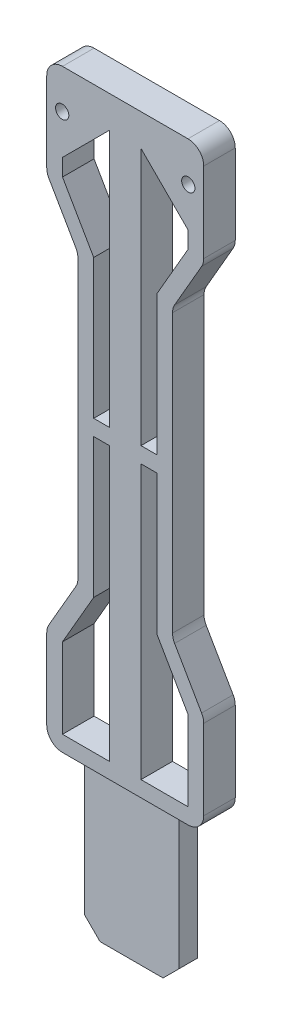
SolidWorks part; units mm, degrees
ref_plane "前视基准面" through (0, 0, 0) normal (0, 0, 1) x (1, 0, 0)
ref_plane "上视基准面" through (0, 0, 0) normal (0, 1, 0) x (1, 0, 0)
ref_plane "右视基准面" through (0, 0, 0) normal (1, 0, 0) x (0, 0, -1)
other "Configuration Table"
sketch "草图1" plane through (0, 0, 0) normal (0, 0, 1) x (1, 0, 0)
  line L1 (-24.9, 94.25) -> (24.9, 94.25)
  line L2 (-24.9, 94.25) -> (-24.9, -94.25)
  line L3 (-24.9, -94.25) -> (24.9, -94.25)
  line L4 (24.9, 94.25) -> (24.9, -94.25)
  line L5 (-24.9, 94.25) -> (24.9, -94.25) construction
  line L6 (-24.9, -94.25) -> (24.9, 94.25) construction
  point P0 (0, 0)
  dimension "D1" = 49.8
  dimension "D2" = 188.5
extrude "凸台-拉伸1" add sketch "草图1" along normal mid plane 10
sketch "草图3" plane through (0, -94.25, 0) normal (0, -1, 0) x (1, 0, 0)
  line L1 (-15, 3) -> (15, 3)
  line L2 (-15, 3) -> (-15, -3)
  line L3 (-15, -3) -> (15, -3)
  line L4 (15, 3) -> (15, -3)
  line L5 (-15, 3) -> (15, -3) construction
  line L6 (-15, -3) -> (15, 3) construction
  point P0 (0, 0)
  dimension "D1" = 6
  dimension "D2" = 30
sketch "草图4" plane through (0, 0, -5) normal (0, 0, -1) x (-1, 0, 0)
  line L0 (-24.9, 62.5) -> (-15, 45.3527)
  line L1 (-24.9, -94.25) -> (-24.9, 94.25) construction
  line L2 (-15, 45.3527) -> (-15, -45.3527)
  line L3 (-15, -45.3527) -> (-24.9, -62.5)
  line L4 (-24.9, -62.5) -> (-24.9, 62.5)
  line L5 (0, 0) -> (0, 82.1988) construction
  line L6 (24.9, -62.5) -> (24.9, 62.5)
  line L7 (15, -45.3527) -> (24.9, -62.5)
  line L8 (15, 45.3527) -> (15, -45.3527)
  line L9 (24.9, 62.5) -> (15, 45.3527)
  point P7 (-15, 0)
  point P11 (-24.9, 0)
  dimension "D1" = 125
  dimension "D2" = 15
  dimension "D3" = 30
extrude "切除-拉伸1" cut sketch "草图4" against normal through all
fillet "圆角1" radius 5 12 edges at (15, -45.3527, 0) (24.9, -62.5, 0) (24.9, -94.25, 0) (-24.9, -94.25, 0) (-24.9, -62.5, 0) (-15, -45.3527, 0) (-15, 45.3527, 0) (-24.9, 62.5, 0) (24.9, 62.5, 0) (15, 45.3527, 0) (-24.9, 94.25, 0) (24.9, 94.25, 0)
sketch "草图5" plane through (0, 0, -5) normal (0, 0, -1) x (-1, 0, 0)
  line L0 (-19.9, 89.25) -> (-19.9, 63.8397)
  line L1 (-19.9, 63.8397) -> (-10, 46.6924)
  line L2 (-10, 46.6924) -> (-10, 2.5)
  line L3 (-10, 2.5) -> (-5, 2.5)
  line L4 (-5, 2.5) -> (-5, 89.25)
  line L5 (-5, 89.25) -> (-19.9, 89.25)
  line L6 (0, 0) -> (52.13, 0) construction
  line L7 (-19.9, 94.25) -> (19.9, 94.25) construction
  line L8 (-15.6699, 46.513) -> (-24.2301, 61.3397) construction
  line L9 (-24.9, 63.8397) -> (-24.9, 89.25) construction
  line L10 (-15, -44.013) -> (-15, 44.013) construction
  line L11 (0, -23.1926) -> (0, 23.1926) construction
  line L12 (5, 89.25) -> (19.9, 89.25)
  line L13 (5, 2.5) -> (5, 89.25)
  line L14 (10, 2.5) -> (5, 2.5)
  line L15 (10, 46.6924) -> (10, 2.5)
  line L16 (19.9, 63.8397) -> (10, 46.6924)
  line L17 (19.9, 89.25) -> (19.9, 63.8397)
  line L18 (19.9, -89.25) -> (19.9, -63.8397)
  line L19 (19.9, -63.8397) -> (10, -46.6924)
  line L20 (10, -46.6924) -> (10, -2.5)
  line L21 (10, -2.5) -> (5, -2.5)
  line L22 (5, -2.5) -> (5, -89.25)
  line L23 (5, -89.25) -> (19.9, -89.25)
  line L24 (-5, -89.25) -> (-19.9, -89.25)
  line L25 (-5, -2.5) -> (-5, -89.25)
  line L26 (-10, -2.5) -> (-5, -2.5)
  line L27 (-10, -46.6924) -> (-10, -2.5)
  line L28 (-19.9, -63.8397) -> (-10, -46.6924)
  line L29 (-19.9, -89.25) -> (-19.9, -63.8397)
  point P15 (-24.9, 76.5449)
  dimension "D1" = 5
  dimension "D2" = 5
  dimension "D3" = 5
  dimension "D4" = 5
  dimension "D5" = 5
  dimension "D6" = 5
extrude "切除-拉伸2" cut sketch "草图5" against normal through all
chamfer "倒角2" distance 20 angle 45 2 edges at (-19.9, 89.25, 0) (19.9, 89.25, 0)
extrude "凸台-拉伸2" add sketch "草图3" along normal blind 48
chamfer "倒角3" distance 5 angle 45 2 edges at (-15, -142.25, 0) (15, -142.25, 0)
sketch "草图6" plane through (0, 0, 5) normal (0, 0, 1) x (1, 0, 0)
  line L0 (0, 0) -> (0, 141.7228) construction
  line L1 (19.9, 94.25) -> (-19.9, 94.25) construction
  circle A0 centre (-20, 81.75) radius 2.1
  circle A1 centre (20, 81.75) radius 2.1
  dimension "D1" = 4.2
  dimension "D2" = 12.5
  dimension "D3" = 40
extrude "切除-拉伸6" cut sketch "草图6" against normal through all
sketch "草图7" plane through (0, 0, -5) normal (0, 0, -1) x (-1, 0, 0)
  circle A0 centre (20, 81.75) radius 3.7
  circle A1 centre (-20, 81.75) radius 3.7
  dimension "D1" = 7.4
extrude "切除-拉伸7" cut sketch "草图7" against normal blind 5
